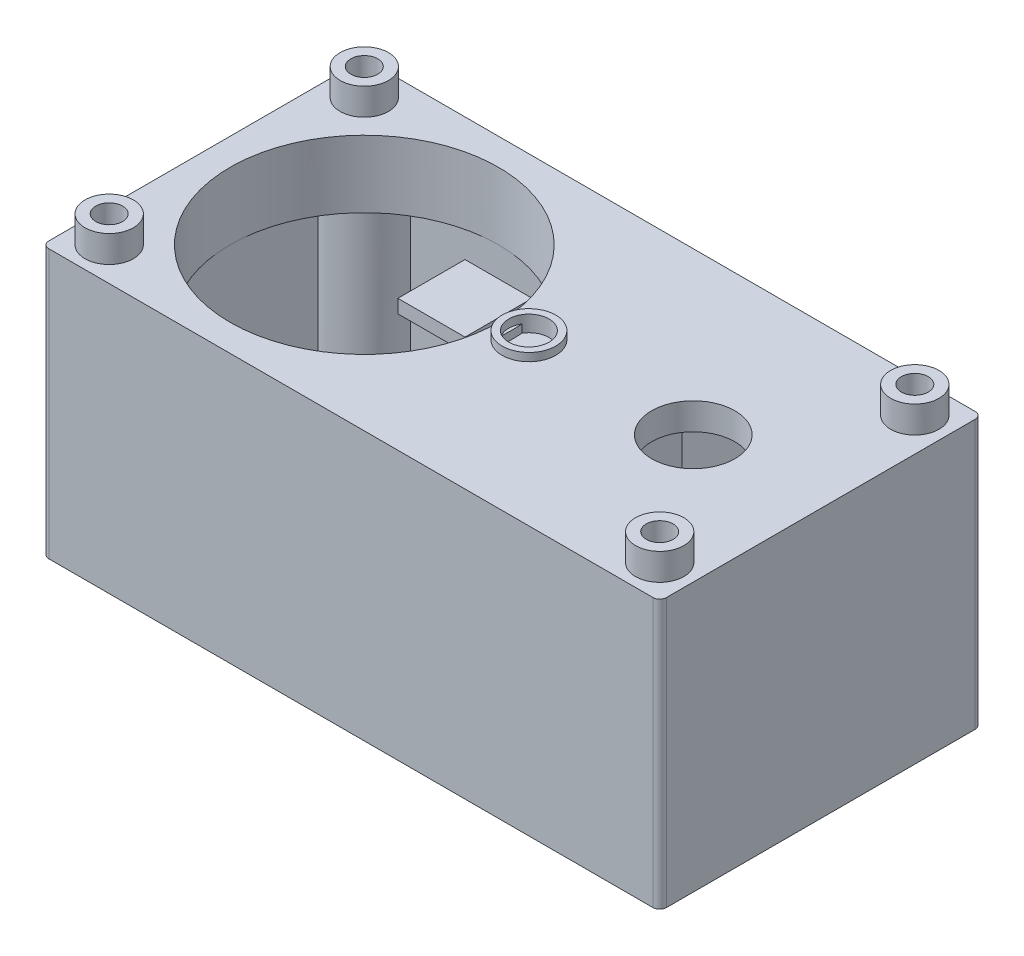
SolidWorks part; units mm, degrees
ref_plane "Front Plane" through (0, 0, 0) normal (0, 0, 1) x (1, 0, 0)
ref_plane "Top Plane" through (0, 0, 0) normal (0, 1, 0) x (1, 0, 0)
ref_plane "Right Plane" through (0, 0, 0) normal (1, 0, 0) x (0, 0, -1)
sketch "Sketch1" plane through (0, 0, 0) normal (0, 1, 0) x (1, 0, 0)
  line L0 (0, 0) -> (0, -6) construction
  line L1 (-11.5, 6) -> (11.5, 6)
  line L2 (-11.5, 6) -> (-11.5, -6)
  line L3 (-11.5, -6) -> (11.5, -6)
  line L4 (11.5, 6) -> (11.5, -6)
  line L5 (-11.5, 6) -> (11.5, -6) construction
  line L6 (-11.5, -6) -> (11.5, 6) construction
  circle A0 centre (-10.25, 4.75) radius 0.5
  circle A1 centre (-10.25, -4.75) radius 0.5
  circle A2 centre (10.25, -4.75) radius 0.5
  circle A3 centre (10.25, 4.75) radius 0.5
  point P0 (0, 0)
  dimension "D3" = 1
  dimension "D4" = 1.25
  dimension "D1" = 12
  dimension "D2" = 23
  dimension "D5" = 1.25
  dimension "D6" = 1.25
extrude "Boss-Extrude1" add sketch "Sketch1" along normal blind 10
shell "Shell1" thickness 1 removed face at (0, 0, 0)
extrude "Extrude-Thin1" add sketch "Sketch1<3>" along normal blind 1 from offset 10 thin contours A3 | A2 | A1 | A0 thin type one direction wall 0.4
sketch "Sketch1<3>" plane through (0, 0, 0) normal (0, 1, 0) x (1, 0, 0) same geometry as "Sketch1"
sketch "Sketch2" plane through (0, 10, 0) normal (0, 1, 0) x (1, 0, 0)
  line L0 (11.5, 6) -> (11.5, -6) construction
  line L1 (-11.5, 6) -> (-11.5, -6) construction
  circle A0 centre (-5.5, 0) radius 5
  circle A1 centre (6.75, 0) radius 1.55
  circle A2 centre (0.63, 0) radius 0.75
  point P8 (0, 0)
  point P11 (0, 0)
  dimension "D1" = 3.1
  dimension "D3" = 10
  dimension "D5" = 1.5
  dimension "D2" = 4.75
  dimension "D4" = 6
  dimension "D6" = 6.13
extrude "Cut-Extrude1" cut sketch "Sketch2" against normal up to next contours A0 | A1 region at (-5.5, 10, 0) region at (6.75, 10, 0)
extrude "Extrude-Thin2" add sketch "Sketch2<3>" along normal blind 0.3 thin contours A2 thin type one direction wall 0.25
sketch "Sketch2<3>" plane through (0, 10, 0) normal (0, 1, 0) x (1, 0, 0) same geometry as "Sketch2"
sketch "Sketch5" plane through (0, 10, 0) normal (0, 1, 0) x (1, 0, 0)
  circle A1 centre (0.63, 0) radius 0.75
  circle A2 centre (0.63, 0) radius 0.75
  dimension "D1" = 0
extrude "Cut-Extrude2" cut sketch "Sketch5" against normal blind 0.3
sketch "Sketch6" plane through (0, 9, 0) normal (0, -1, 0) x (1, 0, 0)
  line L0 (4.575, 5) -> (2.95, 3.375)
  line L1 (-8.771, 5) -> (8.771, 5) construction
  line L2 (2.95, 3.375) -> (2.95, -3.375)
  line L3 (2.95, -3.375) -> (4.575, -5)
  line L4 (8.771, -5) -> (-5.5, -5) construction
  line L5 (10.5, 3.271) -> (10.5, -3.271) construction
  point P10 (0, 0)
  dimension "D1" = 7.55
  dimension "D2" = 135
  dimension "D3" = 135
  dimension "D4" = 6.75
extrude "Extrude-Thin3" add sketch "Sketch6" along normal blind 5 thin thin type one direction wall 0.5
extrude "Extrude-Thin4" add sketch "Sketch2<5>" against normal blind 2.5 separate body thin contours A0 thin type one direction wall 0.5
sketch "Sketch2<5>" plane through (0, 10, 0) normal (0, 1, 0) x (1, 0, 0) same geometry as "Sketch2"
sketch "Sketch7" plane through (0, 10, 0) normal (0, 1, 0) x (1, 0, 0)
  line L0 (-5.5, 5) -> (-7.7913, 5) construction
  line L1 (-6.75, 5) -> (-4.25, 5)
  line L2 (-6.75, 5) -> (-6.75, 2.5)
  line L3 (-6.75, 2.5) -> (-4.25, 2.5)
  line L4 (-4.25, 5) -> (-4.25, 2.5)
  line L5 (-5.5, 0) -> (-7.7695, 0) construction
  line L6 (-4.25, -5) -> (-4.25, -2.5)
  line L7 (-6.75, -2.5) -> (-4.25, -2.5)
  line L8 (-6.75, -5) -> (-6.75, -2.5)
  line L9 (-6.75, -5) -> (-4.25, -5)
  point P6 (-5.5, 2.5)
  dimension "D1" = 2.5
extrude "Boss-Extrude2" add sketch "Sketch7" against normal blind 0.5 from offset 3.6 offset against normal yes
fillet "Fillet1" radius 0.25 4 edges at (11.5, 5, 6) (11.5, 5, -6) (-11.5, 5, -6) (-11.5, 5, 6)
